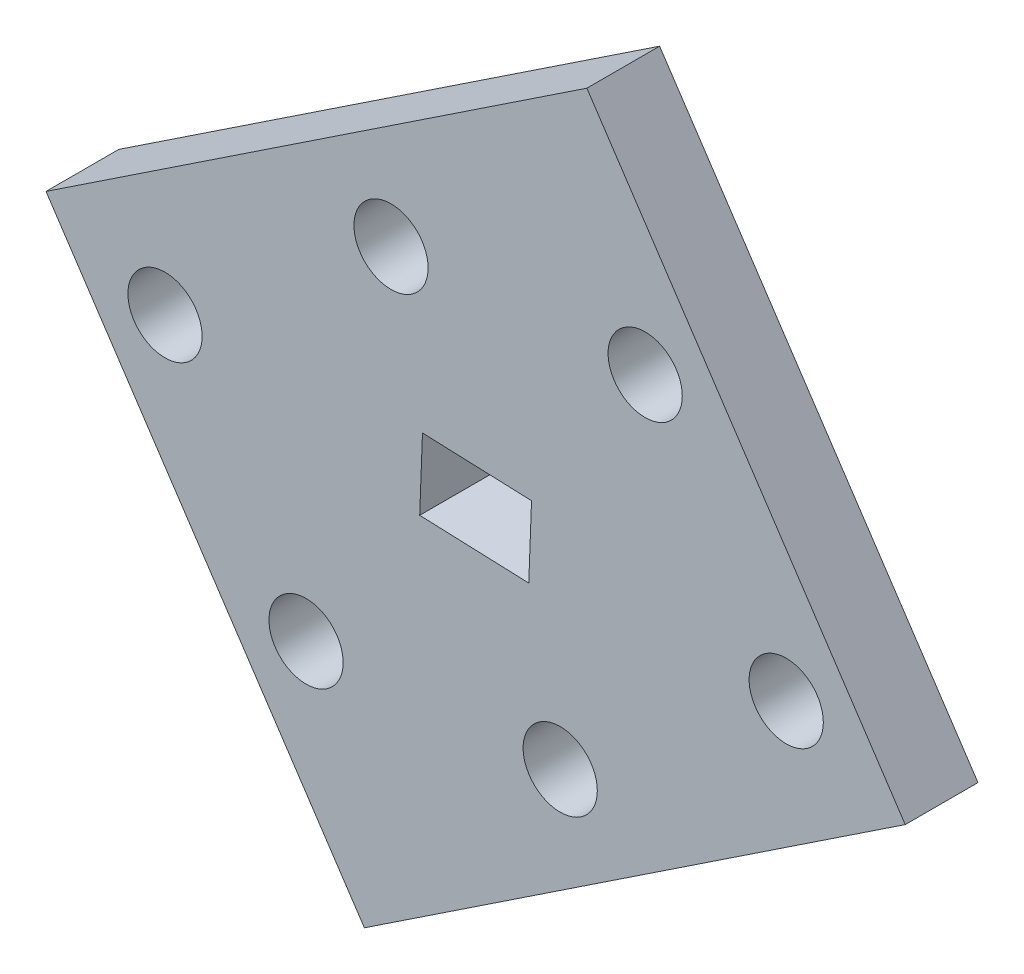
SolidWorks part; units mm, degrees
ref_plane "Front Plane" through (0, 0, 0) normal (0, 0, 1) x (1, 0, 0)
ref_plane "Top Plane" through (0, 0, 0) normal (0, 1, 0) x (1, 0, 0)
ref_plane "Right Plane" through (0, 0, 0) normal (1, 0, 0) x (0, 0, -1)
sketch "Sketch1" plane through (0, 0, 0) normal (0, 0, 1) x (1, 0, 0)
  line L0 (-3.662, -82.9082) -> (70.6732, -33.4555)
  line L1 (-3.662, -82.9082) -> (-47.4195, -17.1337)
  line L2 (70.6732, -33.4555) -> (26.9157, 32.319)
  line L3 (-47.4195, -17.1337) -> (26.9157, 32.319)
  line L4 (-3.662, -82.9082) -> (26.9157, 32.319) construction
  line L5 (70.6732, -33.4555) -> (-47.4195, -17.1337) construction
  line L6 (54.3159, -26.9219) -> (-31.0622, -23.6673) construction
  circle A2 centre (0, 0) radius 5.1
  circle A3 centre (0, 0) radius 5.1
  circle A5 centre (34.9296, 2.2187) radius 5.1
  circle A6 centre (34.9296, 2.2187) radius 5.1
  circle A9 centre (54.3159, -26.9219) radius 5.1
  circle A10 centre (54.3159, -26.9219) radius 5.1
  circle A14 centre (23.2537, -50.5892) radius 5.1
  circle A15 centre (23.2537, -50.5892) radius 5.1
  circle A19 centre (-11.6759, -52.8079) radius 5.1
  circle A20 centre (-11.6759, -52.8079) radius 5.1
  circle A22 centre (-31.0622, -23.6673) radius 5.1
  circle A23 centre (-31.0622, -23.6673) radius 5.1
  point P0 (11.6268, -25.2946)
  point P1 (11.6268, -25.2946)
  dimension "D2" = 0.1
  dimension "D3" = 0.1
  dimension "D4" = 0.1
  dimension "D5" = 0.1
  dimension "D7" = 12
  dimension "D8" = 10
  dimension "D9" = 10
  dimension "D1" = 0.1
  dimension "D6" = 0.1
extrude "Boss-Extrude1" add sketch "Sketch1" against normal blind 10
sketch "Sketch2" plane through (0, 0, 0) normal (0, 0, 1) x (1, 0, 0)
  line L0 (4.3227, -20.0125) -> (19.3119, -20.5839)
  line L1 (4.3227, -20.0125) -> (3.9418, -30.0053)
  line L2 (19.3119, -20.5839) -> (18.9309, -30.5767)
  line L3 (3.9418, -30.0053) -> (18.9309, -30.5767)
  line L4 (4.3227, -20.0125) -> (18.9309, -30.5767) construction
  line L5 (19.3119, -20.5839) -> (3.9418, -30.0053) construction
  line L7 (54.3159, -26.9219) -> (-31.0622, -23.6673) construction
  point P1 (11.6268, -25.2946)
  dimension "D1" = 15
  dimension "D2" = 10
extrude "Cut-Extrude1" cut sketch "Sketch2" against normal up to next
